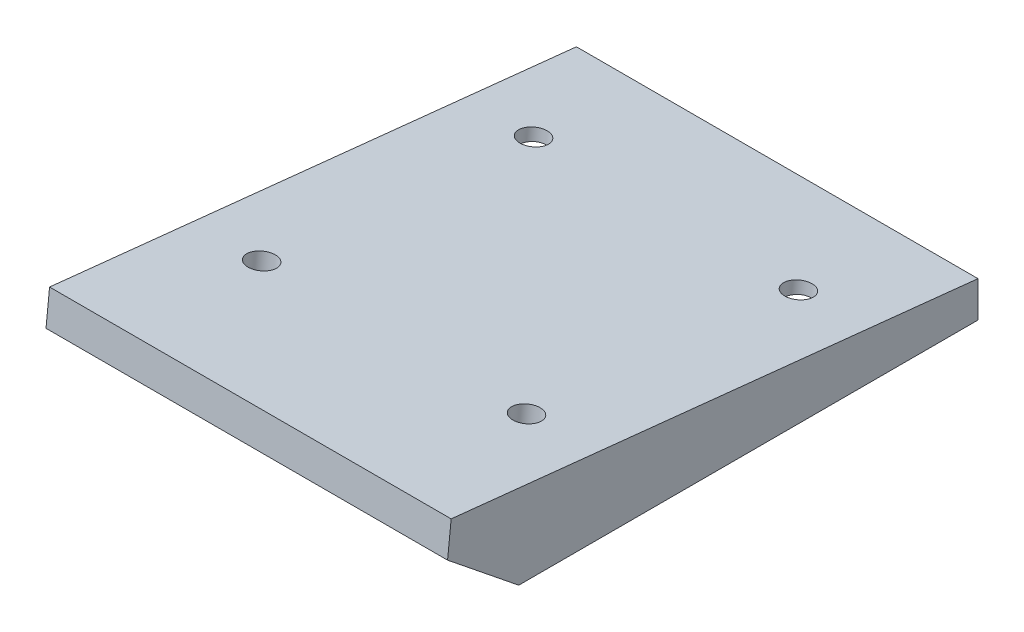
SolidWorks part; units mm, degrees
note: '?' marks a value the reader was unsure of.
ref_plane "Plan de face" through (0, 0, 0) normal (0, 0, 1) x (1, 0, 0)
ref_plane "Plan de dessus" through (0, 0, 0) normal (0, 1, 0) x (1, 0, 0)
ref_plane "Plan de droite" through (0, 0, 0) normal (1, 0, 0) x (0, 0, -1)
sketch "Esquisse1" plane through (0, 0, 0) normal (1, 0, 0) x (0, 0, -1)
  line L3 (53.75, 4.2) -> (-7.9104, 10.6808)
  line L4 (-8.3285, 6.7027) -> (-7.9104, 10.6808)
  line L5 (0, 0) -> (-8.3285, 6.7027)
  line L8 (53.75, 0) -> (53.75, 4.2)
  line L9 (0, 0) -> (53.75, 0)
  dimension "D1" = 6
  dimension "D2" = 53.75
  dimension "D3" = 4
  dimension "D4" = 62
  dimension "D5" = 4.2
extrude "Boss.-Extru.1" add sketch "Esquisse1" against normal offset from surface 1 and the other way offset from surface (23.5 mm away) 1
sketch "Esquisse2" plane through (0, 0, 0) normal (0, -1, 0) x (1, 0, 0)
  line L0 (-22.5, 0) -> (-22.5, -54) construction
  line L1 (-22.6, 0) -> (22.6, 0)
  line L2 (-22.6, 0) -> (-22.6, -53.75)
  line L3 (-22.6, -53.75) -> (22.6, -53.75)
  line L4 (22.6, 0) -> (22.6, -53.75)
  line L5 (-23.5, 0) -> (23.5, 0) construction
  line L6 (-23.5, -53.75) -> (23.5, -53.75) construction
  point P6 (0, -53.75)
  dimension "D1" = 0.1
extrude "Enlèv. mat.-Extru.1" cut sketch "Esquisse2" against normal blind 4.05
sketch "Esquisse3" plane through (0, 9.7417, -1.0239) normal (0, 0.9945, -0.1045) x (1, 0, 0)
  circle A0 centre (-15.5, 39.929) radius 1.6
  circle A1 centre (15.5, 39.929) radius 1.6
  circle A2 centre (15.5, 7.929) radius 1.6
  circle A3 centre (-15.5, 7.929) radius 1.6
extrude "Enlèv. mat.-Extru.2" cut sketch "Esquisse3" against normal up to next
ref_axis "Axe1" through (15.5, -0.6504, -40.0806) along (0, 0.9945, -0.1045)?
ref_axis "Axe2" through (15.5, -1.978, -7.7648) along (0, 0.9945, -0.1045)?
ref_axis "Axe5" through (-15.5, -2.4898, -7.711) along (0, 0.9945, -0.1045)?
ref_axis "Axe6" through (-15.5, -2.3877, -39.898) along (0, 0.9945, -0.1045)?
hole_wizard "Trou pour taraudage pour trou taraudé M31" positions "Esquisse6" profile "Esquisse5" hole size "M3" standard "ISO"
sketch "Esquisse6" plane through (0, 0, 0) normal (0, -0.779, 0.627) x (-1, 0, 0)
  point P0 (13.5, -5.5483)
  point P3 (-13.5, -5.5483)
sketch "Esquisse5" plane through (-13.5, 3.4786, 4.3223) normal (1, 0, 0) x (0, -0.627, -0.779)
  line L0 (0, 0) -> (0, 5.7511)
  line L1 (0, 5.7511) -> (1.25, 5)
  line L2 (1.25, 5) -> (1.25, 0)
  line L5 (1.25, 0) -> (0, 0)
  line L10 (0, 5.7511) -> (-1.25, 5) construction
  line L11 (0, -6.35) -> (0, 107.95) construction
  dimension "Diamètre du perçage" = 2.5
  dimension "Profondeur du perçage" = 5
  dimension "Angle de pointe" = 118
